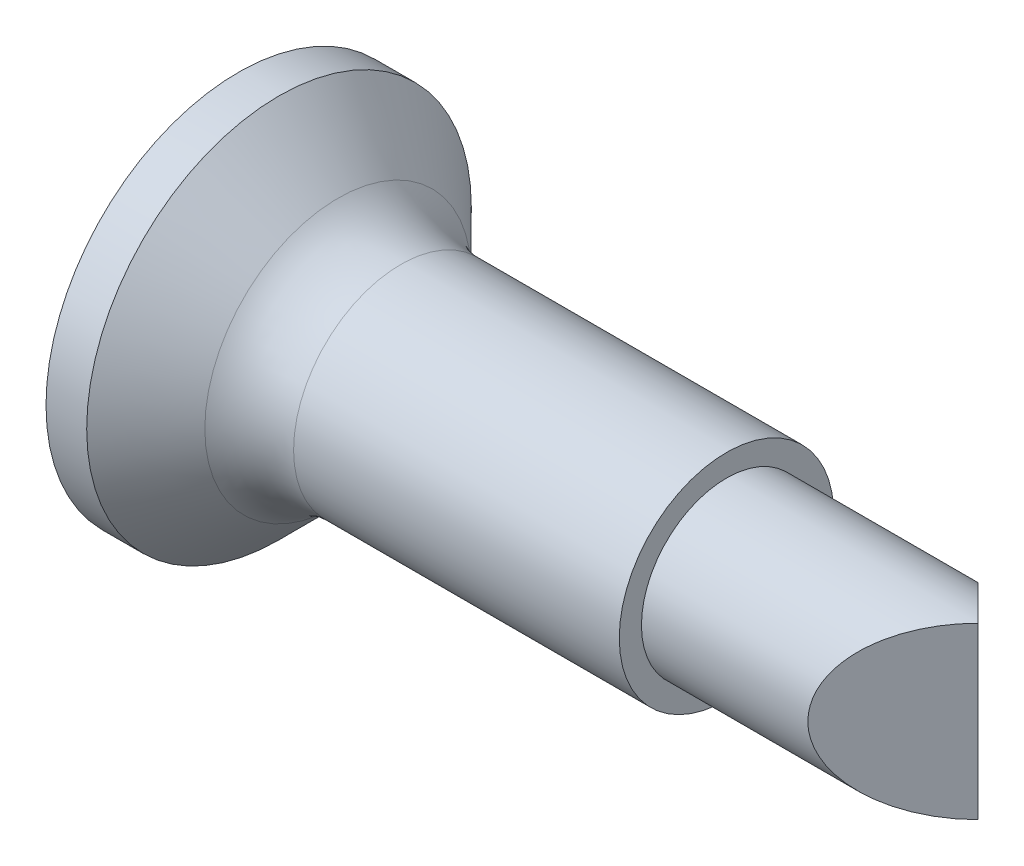
SolidWorks part; units mm, degrees
ref_plane "Front" through (0, 0, 0) normal (0, 0, 1) x (1, 0, 0)
ref_plane "Top" through (0, 0, 0) normal (0, 1, 0) x (1, 0, 0)
ref_plane "Right" through (0, 0, 0) normal (1, 0, 0) x (0, 0, -1)
sketch "Sketch1" plane through (0, 0, 0) normal (0, 0, 1) x (1, 0, 0)
  line L0 (-68.7142, 0) -> (93.1333, 0) construction
  line L1 (0.7, 2.6) -> (1.25, 2.6)
  line L2 (1.25, 2.6) -> (2.4, 1.45)
  line L3 (2.4, 1.45) -> (7.3, 1.45)
  line L4 (7.3, 1.45) -> (7.3, 1.15)
  line L5 (7.3, 1.15) -> (10.7, 1.15)
  line L6 (10.7, 1.15) -> (10.7, 0)
  line L7 (10.7, 0) -> (0, 0)
  line L8 (2.95, 2.6) -> (2.95, 0.6853) construction
  arc A0 (0.7, 2.6) -> (0, 0) centre (5.1786, 0) ccw
  dimension "D4" = 45
revolve "Base" add sketch "Sketch1" angle 360 about L0
cosmetic thread "ThreadCosmetic1" [suppressed] parameters "D1"=4.9, "D2"=2.3
sketch "Sketch2" plane through (0, 0, 0) normal (0, 1, 0) x (1, 0, 0)
  line L0 (11.3362, 0) -> (14.3992, 0) construction
  line L2 (10.7, 0) -> (-4.3, 15)
  line L3 (-4.3, 15) -> (11.0466, 15)
  line L4 (11.0466, 15) -> (11.0466, -15)
  line L6 (-4.3, -15) -> (11.0466, -15)
  line L7 (10.7, 0) -> (-4.3, -15)
  line L8 (10.7, -1.15) -> (10.7, 1.15) construction
  point P11 (11.0466, 0)
  dimension "D1" = 45
  dimension "D2" = 15
  dimension "D3" = 0.3466
extrude "Cut-Extrude1" cut sketch "Sketch2" against normal through all and the other way through all
sketch "Sketch3" plane through (0, 0, 0) normal (1, 0, 0) x (0, 0, -1)
  line L0 (3.0091, 0) -> (-3.0547, 0) construction
  line L1 (0, -3.1383) -> (0, 3.1839) construction
  line L2 (-0.34, 0.34) -> (-1.7, 0.34)
  line L3 (0.34, -1.7) -> (-0.34, -1.7)
  line L4 (0.34, -1.7) -> (0.34, -0.34)
  line L5 (0.34, 1.7) -> (-0.34, 1.7)
  line L6 (-0.34, -1.7) -> (-0.34, -0.34)
  line L7 (1.7, 0.34) -> (0.34, 0.34)
  line L8 (1.7, 0.34) -> (1.7, -0.34)
  line L9 (1.7, -0.34) -> (0.34, -0.34)
  line L10 (-1.7, 0.34) -> (-1.7, -0.34)
  line L11 (-0.34, 0.34) -> (-0.34, 1.7)
  line L12 (-0.34, -0.34) -> (-1.7, -0.34)
  line L13 (0.34, 0.34) -> (0.34, 1.7)
  dimension "D2" = 3.4
  dimension "D3" = 0.68
  dimension "D4" = 0.68
extrude "CrossRecess" cut sketch "Sketch3" along normal blind 0.85
fillet "Fillet1" radius 1.2 1 edges at (2.4, 0, 1.45)
fillet "Fillet2" radius 0.34 4 edges at (0.4362, -0.34, -0.34) (0.4362, -0.34, 0.34) (0.4362, 0.34, 0.34) (0.4362, 0.34, -0.34)
draft "Draft1" type of draft neutral plane draft angle 25 neutral plane "Right" faces to draft 4 face at (0.5715, 0, 1.7) face at (0.5715, 1.7, 0) face at (0.5715, -1.7, 0) face at (0.5715, 0, -1.7) neutral plane through (0, 0, 0) neutral plane normal (1, 0, 0) reverse direction yes parameters "D1"=25
sketch "Sketch4" plane through (0, 0, 0) normal (1, 0, 0) x (0, 0, -1)
  line L0 (-3.0851, 0) -> (3.2219, 0) construction
  line L1 (0, -3.0623) -> (0, 2.9255) construction
  line L2 (0, 0) -> (2.482, 2.482) construction
  line L3 (0, 0) -> (-2.6424, 2.6424) construction
  line L4 (0, 0.5081) -> (1.2021, 1.2021)
  line L5 (1.2021, 1.2021) -> (0.5081, 0)
  line L6 (0, 0.5081) -> (-1.2021, 1.2021)
  line L7 (-1.2021, 1.2021) -> (-0.5081, 0)
  line L8 (-1.2021, -1.2021) -> (-0.5081, 0)
  line L9 (0, -0.5081) -> (-1.2021, -1.2021)
  line L10 (1.2021, -1.2021) -> (0.5081, 0)
  line L11 (0, -0.5081) -> (1.2021, -1.2021)
  dimension "D1" = 45
  dimension "D2" = 15
  dimension "D3" = 3.4
extrude "Cut-Extrude4" [suppressed] cut sketch "Sketch4" along normal blind 0.85
sketch "Sketch5" plane through (0, 0, 0) normal (0, 0, 1) x (1, 0, 0)
  line L0 (0, 0) -> (11.146, 0) construction
  line L1 (3.3268, 1.7964) -> (3.6732, 1.7964)
  line L2 (3.6732, 1.7964) -> (3.6732, 1.45)
  line L3 (3.6732, 1.45) -> (3.5, 1.15)
  line L4 (3.5, 1.15) -> (3.3268, 1.45)
  line L5 (3.3268, 1.45) -> (3.3268, 1.7964)
  line L6 (0.7, 2.6) -> (0.7, -2.6) construction
  dimension "D2" = 2.3
  dimension "D1" = 2.9
  dimension "D3" = 2.8
revolve "Cut-Revolve10" [suppressed] cut sketch "Sketch5" angle 360 about L0
pattern_linear "LPattern10" [suppressed] count 9 spacing 0.45 along (1, 0, 0) of bodies 105
equation "\"D1@ThreadCosmetic1\" = \"lg@Sketch1\" - \"k@Sketch1\""
equation "\"D2@ThreadCosmetic1\" = \"dp@Sketch1\""
equation "\"D2@Sketch3\" = \"m@Sketch3\""
equation "\"D3@Sketch3\" = \"D4@Sketch3\""
equation "\"D4@Sketch3\" = \"m@Sketch3\" / 5"
equation "\"D1@Fillet2\" = \"D3@Sketch3\" / 2"
equation "\"D3@Sketch4\" = \"m@Sketch3\""
equation "\"D1@Cut-Extrude4\" = \"D1@CrossRecess\""
equation "\"D1@CrossRecess\" = \"k@Sketch1\" / 2"
equation "\"D1@Sketch5\" = \"d@Sketch1\""
equation "\"D2@Sketch5\" = \"dp@Sketch1\""
equation "\"D3@Sketch5\" =\"a@Sketch1\" + \"k@Sketch1\""
equation "\"D3@LPattern10\" =( \"d@Sketch1\" - \"dp@Sketch1\") / 2*1.5"
equation "\"D1@LPattern10\" =(\"lg@Sketch1\" - \"k@Sketch1\" - \"a@Sketch1\") / \"D3@LPattern10\"+1"
